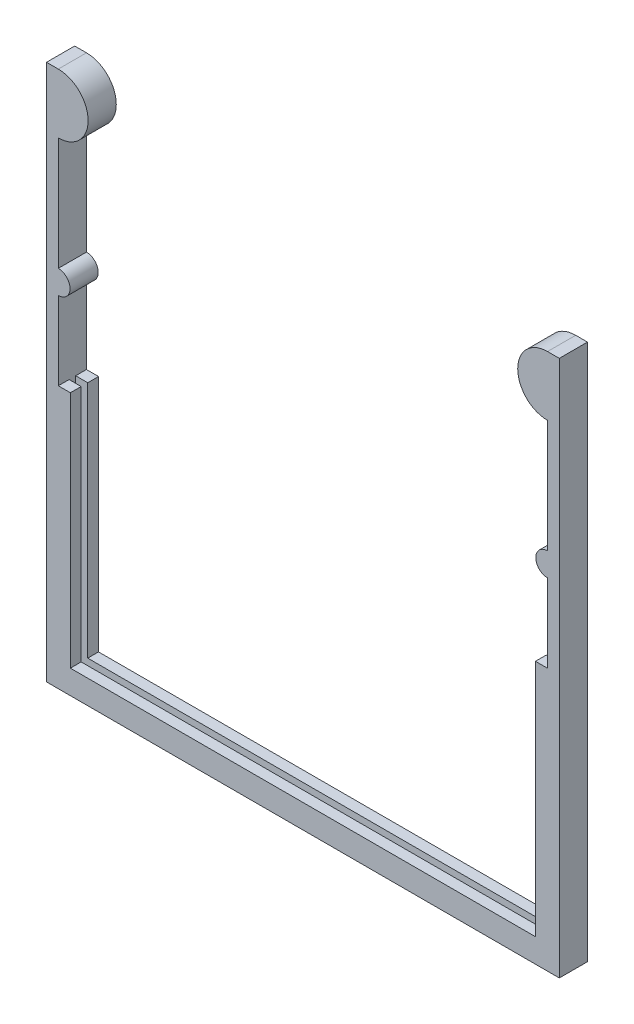
SolidWorks part; units mm, degrees
ref_plane "Front Plane" through (0, 0, 0) normal (0, 0, 1) x (1, 0, 0)
ref_plane "Top Plane" through (0, 0, 0) normal (0, 1, 0) x (1, 0, 0)
ref_plane "Right Plane" through (0, 0, 0) normal (1, 0, 0) x (0, 0, -1)
sketch "Sketch1" plane through (0, 0, 0) normal (0, 0, 1) x (1, 0, 0)
  line L0 (52.1, -43.8) -> (52.1, 26.2) construction
  line L1 (-52.1, -43.8) -> (52.1, -43.8)
  line L2 (-52.1, -43.8) -> (-52.1, 26.2)
  line L3 (-39.908, 46.774) -> (34.574, 46.774)
  line L4 (52.1, -43.8) -> (52.1, 26.2)
  line L5 (-52.1, -43.8) -> (52.1, 43.8) construction
  line L6 (-52.1, 43.8) -> (52.1, -43.8) construction
  line L7 (52.1, 43.8) -> (47.528, 43.8)
  line L8 (52.1, 43.8) -> (52.1, 31.2) construction
  line L9 (52.1, -43.8) -> (52.1, 26.2) construction
  line L10 (0, 0) -> (0, 60.9791) construction
  line L11 (0, 0) -> (0, -2.54) construction
  line L12 (52.1, 31.2) -> (52.1, 43.8) construction
  line L13 (52.1, 31.2) -> (52.1, 43.8)
  line L14 (-52.1, 31.2) -> (-52.1, 43.8)
  line L15 (52.1, -43.8) -> (46.9877, -43.8) construction
  line L16 (52.1, 31.2) -> (34.574, 31.2) construction
  line L17 (-52.1, 31.2) -> (-39.908, 31.2) construction
  line L18 (-52.1, 26.2) -> (52.1, 26.2) construction
  line L19 (-39.908, 31.2) -> (-39.908, 26.2) construction
  line L20 (34.574, 31.2) -> (34.574, 26.2) construction
  line L21 (52.1, 31.2) -> (47.528, 31.2) construction
  line L22 (-39.908, 26.2) -> (34.574, 26.2)
  line L23 (-39.908, 26.2) -> (-39.908, 46.774)
  line L24 (-39.908, 46.774) -> (34.574, 46.774)
  line L25 (34.574, 26.2) -> (34.574, 46.774)
  line L26 (47.528, 31.2) -> (37.368, 31.2) construction
  line L27 (37.368, 46.774) -> (47.528, 46.774)
  line L28 (47.528, 31.2) -> (37.368, 31.2)
  line L29 (47.528, 31.2) -> (47.528, 46.774)
  line L30 (47.528, 46.774) -> (37.368, 46.774)
  line L31 (37.368, 31.2) -> (37.368, 46.774)
  line L32 (-39.908, 43.8) -> (-52.1, 43.8)
  line L33 (37.368, 43.8) -> (34.574, 43.8)
  line L34 (-39.908, 43.8) -> (-39.908, 26.2)
  line L35 (34.574, 43.8) -> (34.574, 26.2)
  line L36 (0, -43.8) -> (0, -46.34) construction
  arc A0 (52.1, 31.2) -> (52.1, 26.2) centre (52.1, 28.7) ccw
  arc A1 (-52.1, 31.2) -> (-52.1, 26.2) centre (-52.1, 28.7) cw
  point P0 (0, 0)
  dimension "D2" = 104.2
  dimension "D3" = 5
  dimension "D4" = 5
  dimension "D5" = 70
  dimension "D6" = 5.1123
  dimension "D7" = 17.526
  dimension "D8" = 12.192
  dimension "D9" = 4.572
  dimension "D10" = 10.16
  dimension "D11" = 20.574
  dimension "D12" = 2.54
  dimension "D13" = 2.54
  dimension "D14" = 12.6
sketch "Sketch2" plane through (0, 0, 0) normal (0, 0, 1) x (1, 0, 0)
  line L0 (0, -41.26) -> (0, 73.66) construction
  line L1 (-52.1, 67.96) -> (-54.61, 67.96)
  line L2 (-52.1, 43.8) -> (-52.1, 55.26)
  line L3 (-54.61, 9.9292) -> (-54.61, 67.96)
  line L4 (-52.1, 9.54) -> (-49.53, 9.54)
  line L5 (52.1, 31.2) -> (52.1, 43.8) construction
  line L6 (-54.61, -46.34) -> (-54.61, 9.9292)
  line L7 (-49.53, -41.26) -> (-49.53, 9.54)
  line L8 (-52.1, 31.2) -> (-52.1, 43.8)
  line L9 (-52.1, 9.54) -> (-52.1, 26.2)
  line L14 (52.1, 9.54) -> (52.1, 26.2)
  line L19 (52.1, 31.2) -> (52.1, 43.8)
  line L33 (49.53, -41.26) -> (49.53, 9.54)
  line L34 (54.61, -46.34) -> (54.61, 9.9292)
  line L39 (52.1, 9.54) -> (49.53, 9.54)
  line L40 (49.53, -41.26) -> (-49.53, -41.26)
  line L41 (54.61, -46.34) -> (-54.61, -46.34)
  line L43 (54.61, 9.9292) -> (54.61, 67.96)
  line L44 (52.1, 43.8) -> (52.1, 55.26)
  line L45 (52.1, 67.96) -> (54.61, 67.96)
  arc A0 (-52.1, 67.96) -> (-52.1, 55.26) centre (-52.1, 61.61) cw
  arc A1 (52.1, 31.2) -> (52.1, 26.2) centre (52.1, 28.7) ccw construction
  arc A2 (-52.1, 31.2) -> (-52.1, 26.2) centre (-52.1, 28.7) cw
  arc A3 (52.1, 31.2) -> (52.1, 26.2) centre (52.1, 28.7) ccw
  arc A4 (52.1, 67.96) -> (52.1, 55.26) centre (52.1, 61.61) ccw
  point P19 (0, -46.34)
  dimension "D1" = 5.08
  dimension "D2" = 49.53
  dimension "D3" = 50.8
  dimension "D4" = 2.54
  dimension "D6" = 114.3
  dimension "D7" = 12.7
sketch "Sketch3" plane through (0, 0, 0) normal (0, 0, 1) x (1, 0, 0)
  line L0 (-52.1, 9.54) -> (-52.1, -43.8)
  line L1 (-52.1, 9.54) -> (-49.53, 9.54)
  line L4 (52.1, 9.54) -> (49.53, 9.54) construction
  line L5 (0, -43.8) -> (0, 39.6741) construction
  line L9 (52.1, 9.54) -> (49.53, 9.54)
  line L15 (52.1, 9.54) -> (52.1, -43.8)
  line L16 (-52.1, -43.8) -> (52.1, -43.8)
  line L17 (49.53, 9.54) -> (-49.53, 9.54)
  line L18 (0, -41.26) -> (0, 73.66) construction
  line L19 (0, 9.54) -> (0, -43.8)
extrude "Boss-Extrude1" add sketch "Sketch2" along normal blind 3 and the other way blind 3
extrude "Cut-Extrude1" cut sketch "Sketch3" against normal blind 0.7 and the other way blind 0.7 contours L17 L1 L0 L16 L15 L9
sketch "Sketch4" plane through (0, 0, 0) normal (0, 0, 1) x (1, 0, 0)
  line L0 (0, -43.8) -> (0, 32.3652) construction
  line L1 (49.53, 9.54) -> (-49.53, 9.54) construction
  line L2 (49.53, -41.26) -> (49.53, 9.54) construction
  line L3 (49.53, -41.26) -> (-49.53, -41.26) construction
  line L4 (3.81, 1.92) -> (3.81, -41.26)
  line L5 (49.53, 9.54) -> (-49.53, 9.54)
  line L6 (49.53, -37.45) -> (49.53, 5.73)
  line L7 (45.75, -41.26) -> (3.81, -41.26)
  line L8 (0, -43.8) -> (0, 39.6741) construction
  line L9 (-52.1, 9.54) -> (-52.1, -43.8)
  line L10 (3.81, 1.92) -> (45.75, -41.26)
  line L11 (7.62, 5.73) -> (49.53, 5.73)
  line L12 (-49.53, 9.54) -> (-52.1, 9.54)
  line L13 (-7.62, 5.73) -> (-49.53, -37.45)
  line L14 (7.62, 5.73) -> (49.53, -37.45)
  line L15 (49.53, 9.54) -> (52.1, 9.54)
  line L16 (52.1, 9.54) -> (52.1, -43.8)
  line L17 (52.1, -43.8) -> (-52.1, -43.8)
  line L18 (0, -43.8) -> (0, 9.54)
  line L19 (-7.62, 5.73) -> (-49.53, 5.73)
  line L20 (-3.81, 1.92) -> (-45.75, -41.26)
  line L21 (-45.75, -41.26) -> (-3.81, -41.26)
  line L22 (-49.53, -37.45) -> (-49.53, 5.73)
  line L23 (-3.81, 1.92) -> (-3.81, -41.26)
  dimension "D2" = 3.81
  dimension "D3" = 6.35
  dimension "D4" = 3.81
  dimension "D5" = 6.35
  dimension "D9" = 7.62
  dimension "D10" = 7.62
